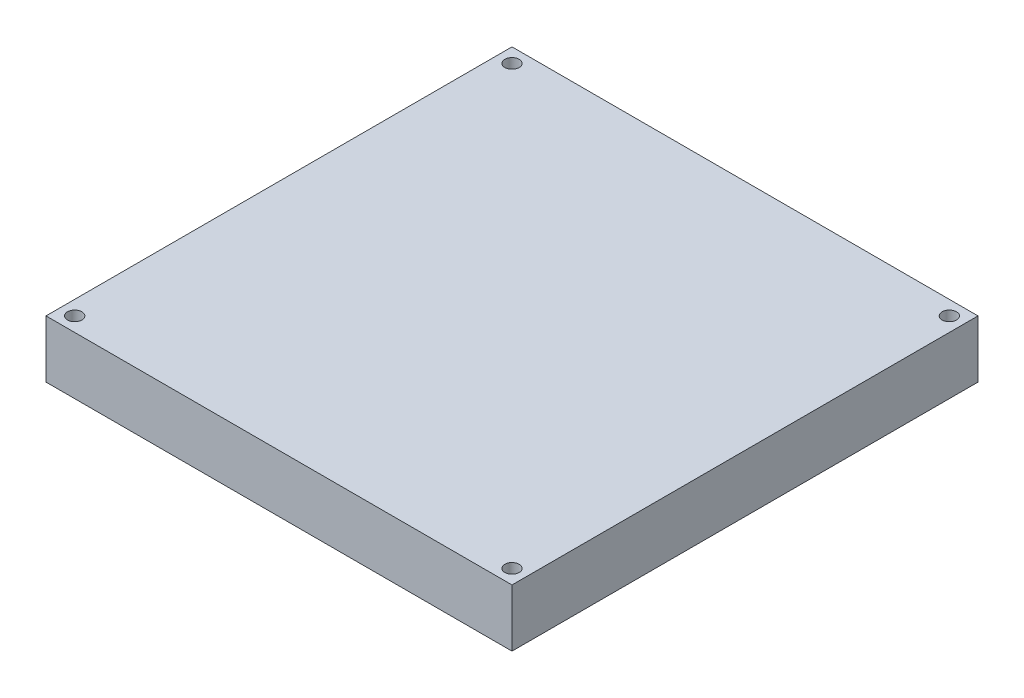
SolidWorks part; units mm, degrees
ref_plane "Front Plane" through (0, 0, 0) normal (0, 0, 1) x (1, 0, 0)
ref_plane "Top Plane" through (0, 0, 0) normal (0, 1, 0) x (1, 0, 0)
ref_plane "Right Plane" through (0, 0, 0) normal (1, 0, 0) x (0, 0, -1)
sketch "Sketch1" plane through (0, 0, 0) normal (0, 1, 0) x (1, 0, 0)
  line L1 (16.25, -16.25) -> (-16.25, -16.25)
  line L2 (16.25, -16.25) -> (16.25, 16.25)
  line L3 (16.25, 16.25) -> (-16.25, 16.25)
  line L4 (-16.25, -16.25) -> (-16.25, 16.25)
  line L5 (16.25, -16.25) -> (-16.25, 16.25) construction
  line L6 (16.25, 16.25) -> (-16.25, -16.25) construction
  point P0 (0, 0)
  dimension "D1" = 32.5
extrude "Boss-Extrude1" add sketch "Sketch1" along normal blind 4
sketch "Sketch2" plane through (0, 4, 0) normal (0, 1, 0) x (1, 0, 0)
  line L1 (15.25, -15.25) -> (-15.25, -15.25)
  line L2 (15.25, -15.25) -> (15.25, 15.25)
  line L3 (15.25, 15.25) -> (-15.25, 15.25)
  line L4 (-15.25, -15.25) -> (-15.25, 15.25)
  line L5 (15.25, -15.25) -> (-15.25, 15.25) construction
  line L6 (15.25, 15.25) -> (-15.25, -15.25) construction
  point P0 (0, 0)
  point P7 (-15.25, -15.25)
  point P8 (-15.25, 15.25)
  point P9 (15.25, -15.25)
  point P10 (15.25, 15.25)
  dimension "D1" = 30.5
hole_wizard "Ø1.0mm Press Dowel Hole1" positions "Sketch3" profile "Sketch4" hole size "Ø1.0" standard "ANSI Metric" end condition through all
sketch "Sketch3" plane through (0, 4, 0) normal (0, 1, 0) x (1, 0, 0)
  point P0 (-15.25, 15.25)
  point P3 (15.25, 15.25)
  point P6 (15.25, -15.25)
  point P9 (-15.25, -15.25)
sketch "Sketch4" plane through (-15.25, 4, -15.25) normal (1, 0, 0) x (0, 0, 1)
  line L0 (0, 0) -> (0, 4)
  line L1 (0, 4) -> (0.5, 4)
  line L2 (0.5, 4) -> (0.5, 0)
  line L5 (0.5, 0) -> (0, 0)
  line L11 (0, -6.35) -> (0, 107.95) construction
  dimension "Thru Hole Dia." = 1
  dimension "Thru Hole Depth" = 4
